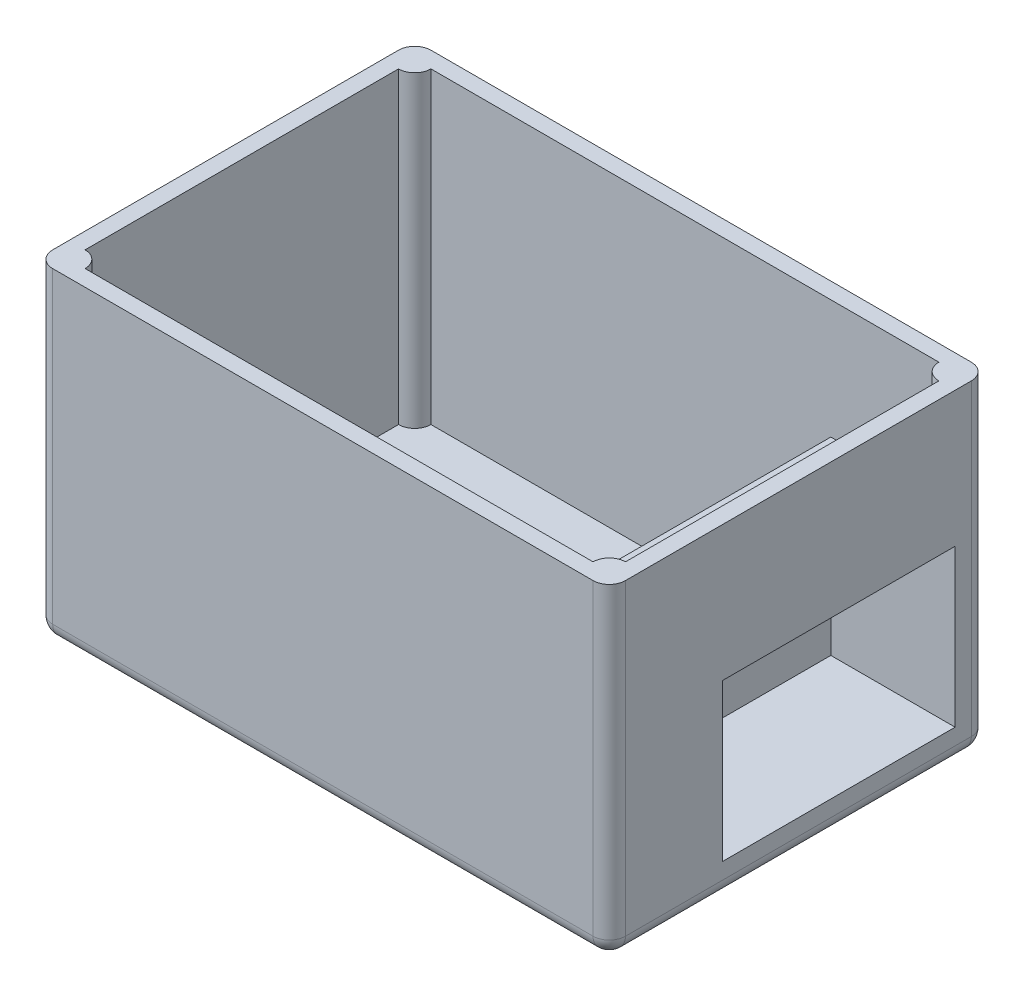
SolidWorks part; units mm, degrees
ref_plane "Alzado" through (0, 0, 0) normal (0, 0, 1) x (1, 0, 0)
ref_plane "Planta" through (0, 0, 0) normal (0, 1, 0) x (1, 0, 0)
ref_plane "Vista lateral" through (0, 0, 0) normal (1, 0, 0) x (0, 0, -1)
sketch "Croquis1" plane through (0, 0, 0) normal (0, 1, 0) x (1, 0, 0)
  line L0 (-52.26, 46.9441) -> (-52.26, -23.0559)
  line L1 (-52.26, -23.0559) -> (53.74, -23.0559)
  line L2 (53.74, -23.0559) -> (53.74, 46.9441)
  line L3 (53.74, 46.9441) -> (-52.26, 46.9441)
  dimension "D1" = 106
  dimension "D2" = 70
extrude "Saliente-Extruir1" add sketch "Croquis1" against normal blind 60
sketch "Croquis2" plane through (0, 0, 0) normal (0, 1, 0) x (1, 0, 0)
  line L0 (-49.26, 43.9441) -> (-49.26, -20.0559)
  line L1 (-49.26, -20.0559) -> (50.74, -20.0559)
  line L2 (50.74, -20.0559) -> (50.74, 43.9441)
  line L3 (50.74, 43.9441) -> (-49.26, 43.9441)
  line L4 (53.74, 46.9441) -> (-52.26, 46.9441) construction
  line L5 (-52.26, 46.9441) -> (-52.26, -23.0559) construction
  line L6 (-52.26, -23.0559) -> (53.74, -23.0559) construction
  line L7 (53.74, -23.0559) -> (53.74, 46.9441) construction
  dimension "D1" = 3
  dimension "D2" = 3
  dimension "D3" = 3
  dimension "D4" = 3
extrude "Cortar-Extruir1" cut sketch "Croquis2" against normal blind 57 contours L0 L1 L2 L3
sketch "Croquis3" plane through (0, 0, 0) normal (0, 1, 0) x (1, 0, 0)
  circle A0 centre (-49.26, 43.9441) radius 3
  circle A1 centre (-49.26, -20.0559) radius 3
  circle A2 centre (50.74, -20.0559) radius 3
  circle A3 centre (50.74, 43.9441) radius 3
  dimension "D1" = 6
  dimension "D2" = 6
  dimension "D3" = 6
  dimension "D4" = 6
extrude "Saliente-Extruir2" add sketch "Croquis3" against normal blind 57
fillet "Redondeo1" radius 3 1 edges at (-52.26, -30, -46.9441) type face fillet first side face at (0.74, -30, -46.9441) second side face at (-52.26, -30, -11.9441)
fillet "Redondeo3" radius 3 1 edges at (-52.26, -30, 23.0559) type face fillet first side face at (0.74, -30, 23.0559) second side face at (-52.26, -30, -10.4441)
fillet "Redondeo4" radius 3 1 edges at (53.74, -30, 23.0559) type face fillet first side face at (53.74, -30, -11.9441) second side face at (2.24, -30, 23.0559)
fillet "Redondeo5" radius 3 1 edges at (53.74, -30, -46.9441) type face fillet first side face at (2.24, -30, -46.9441) second side face at (53.74, -30, -13.4441)
fillet "Redondeo6" radius 3 8 edges at (-51.3813, -60, -46.0654) (-52.26, -60, -11.9441) (-51.3813, -60, 22.1772) (0.74, -60, 23.0559) (52.8613, -60, 22.1772) (53.74, -60, -11.9441) (52.8613, -60, -46.0654) (0.74, -60, -46.9441)
sketch "Croquis4" plane through (53.74, 0, 0) normal (1, 0, 0) x (0, 0, -1)
  line L0 (-20.0559, -57) -> (43.9441, -57)
  line L1 (-20.0559, 0) -> (-20.0559, -57) construction
  line L2 (43.9441, -57) -> (43.9441, -22)
  line L3 (-20.0559, 0) -> (43.9441, 0) construction
  line L4 (43.9441, -22) -> (-20.0559, -22)
  line L5 (-20.0559, -22) -> (-20.0559, -57)
  line L6 (43.9441, -57) -> (43.9441, 0) construction
  dimension "D1" = 0
  dimension "D2" = 35
  dimension "D3" = 0
  dimension "D4" = 22
extrude "Saliente-Extruir4" add sketch "Croquis4" against normal blind 26 contours L4 L5 L0 L2
sketch "Croquis6" plane through (53.74, 0, 0) normal (1, 0, 0) x (0, 0, -1)
  line L0 (40.9441, -54) -> (-2.0559, -54)
  line L1 (43.9441, -57) -> (43.9441, 0) construction
  line L2 (-2.0559, -54) -> (-2.0559, -25)
  line L3 (-2.0559, -25) -> (40.9441, -25)
  line L5 (40.9441, -25) -> (40.9441, -54)
  line L8 (-20.0559, 0) -> (43.9441, 0) construction
  dimension "D1" = 3
  dimension "D2" = 25
  dimension "D3" = 29
  dimension "D4" = 43
extrude "Cortar-Extruir5" cut sketch "Croquis6" against normal blind 23
sketch "Croquis8" plane through (0, -22, 0) normal (0, 1, 0) x (1, 0, 0)
  line L0 (35.74, -5.3635) -> (35.74, -14.5559)
  line L1 (35.74, -14.5559) -> (44.9324, -14.5559)
  line L2 (44.9324, -14.5559) -> (44.9324, -5.3635)
  line L3 (44.9324, -5.3635) -> (35.74, -5.3635)
  line L4 (27.74, 43.9441) -> (27.74, -20.0559) construction
  line L13 (27.74, -20.0559) -> (47.74, -20.0559) construction
  dimension "D1" = 13
  dimension "D2" = 8
  dimension "D3" = 5.5
extrude "Cortar-Extruir6" cut sketch "Croquis8" against normal blind 10
sketch "Croquis9" plane through (0, 0, 2.0559) normal (0, 0, -1) x (-1, 0, 0)
  line L0 (-48.74, -26.5) -> (-48.74, -52.5)
  line L1 (-48.74, -52.5) -> (-35.74, -52.5)
  line L2 (-35.74, -52.5) -> (-35.74, -26.5)
  line L3 (-35.74, -26.5) -> (-48.74, -26.5)
  line L4 (-30.74, -25) -> (-53.74, -25) construction
  line L5 (-53.74, -25) -> (-53.74, -54) construction
  dimension "D1" = 26
  dimension "D2" = 13
  dimension "D3" = 1.5
  dimension "D4" = 5
extrude "Cortar-Extruir8" cut sketch "Croquis9" against normal blind 12.5
